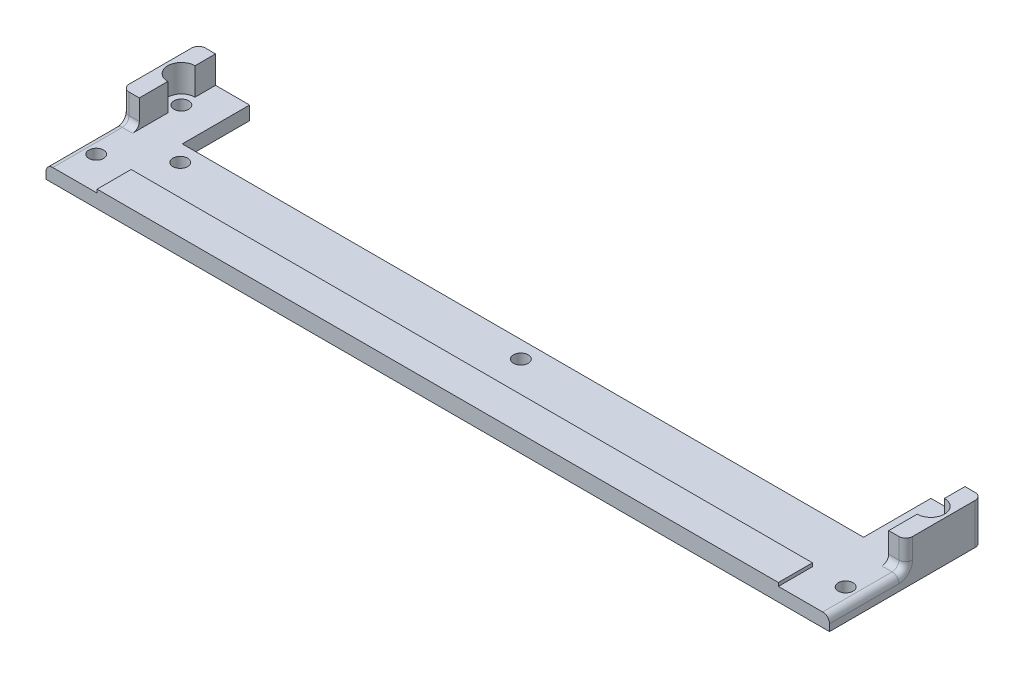
SolidWorks part; units mm, degrees
ref_plane "Front Plane" through (0, 0, 0) normal (0, 0, 1) x (1, 0, 0)
ref_plane "Top Plane" through (0, 0, 0) normal (0, 1, 0) x (1, 0, 0)
ref_plane "Right Plane" through (0, 0, 0) normal (1, 0, 0) x (0, 0, -1)
sketch "Sketch1" plane through (0, 0, 0) normal (0, 1, 0) x (1, 0, 0)
  line L0 (-139.7, 33.3321) -> (-139.7, 40.988)
  line L1 (-127, -15.875) -> (127, -15.875)
  line L2 (-127, -15.875) -> (-127, 15.875)
  line L3 (-127, 15.875) -> (127, 15.875)
  line L4 (127, -15.875) -> (127, 15.875)
  line L5 (-127, -15.875) -> (127, 15.875) construction
  line L6 (-127, 15.875) -> (127, -15.875) construction
  line L7 (-127, -15.875) -> (-146.05, -15.875)
  line L8 (-127, -15.875) -> (-127, 40.988)
  line L9 (-127, 40.988) -> (-146.05, 40.988)
  line L10 (-146.05, -15.875) -> (-146.05, 40.988)
  line L11 (127, -15.875) -> (146.05, -15.875)
  line L12 (127, -15.875) -> (127, 40.988)
  line L13 (127, 40.988) -> (146.05, 40.988)
  line L14 (146.05, -15.875) -> (146.05, 40.988)
  line L15 (-139.7, 23.1721) -> (-139.7, 1.5821)
  line L16 (-139.7, 33.3321) -> (-139.7, 31.0021)
  line L17 (-139.7, 25.5021) -> (-139.7, 23.1721)
  line L18 (-139.7, 1.5821) -> (-139.7, -0.7479)
  line L19 (-139.7, -6.2479) -> (-139.7, -15.875)
  line L20 (0, 15.875) -> (0, -15.875) construction
  line L21 (139.7, 1.5821) -> (139.7, -0.7479)
  line L22 (139.7, -6.2479) -> (139.7, -15.875)
  line L23 (139.7, 23.1721) -> (139.7, 1.5821)
  line L24 (139.7, 25.5021) -> (139.7, 23.1721)
  line L25 (139.7, 33.3321) -> (139.7, 31.0021)
  line L26 (139.7, 33.3321) -> (139.7, 40.988)
  line L27 (139.7, 40.988) -> (139.7, 31.0021)
  line L28 (139.7, 23.1721) -> (139.7, 25.5021)
  line L29 (139.7, 23.1721) -> (139.7, -0.7479)
  line L30 (139.7, -6.2479) -> (139.7, -15.875)
  circle A0 centre (-139.7, 28.2521) radius 2.75
  circle A1 centre (-139.7, -3.4979) radius 2.75
  circle A2 centre (139.7, 28.2521) radius 2.75
  circle A3 centre (139.7, -3.4979) radius 2.75
  arc A4 (-139.7, 33.3321) -> (-139.7, 23.1721) centre (-139.7, 28.2521) ccw
  arc A5 (-139.7, 1.5821) -> (-139.7, -8.5779) centre (-139.7, -3.4979) ccw
  arc A6 (139.7, -8.5779) -> (139.7, 1.5821) centre (139.7, -3.4979) ccw
  arc A7 (139.7, 23.1721) -> (139.7, 33.3321) centre (139.7, 28.2521) ccw
  circle A8 centre (5.588, 9.525) radius 2.75
  circle A9 centre (-121.412, 9.525) radius 2.75
  point P0 (0, 0)
  dimension "D5" = 5.5
  dimension "D6" = 10.16
  dimension "D7" = 10.16
  dimension "D8" = 254
  dimension "D9" = 31.75
  dimension "D11" = 5.5
  dimension "D13" = 5.5
  dimension "D1" = 31.75
  dimension "D2" = 279.4
  dimension "D3" = 292.1
  dimension "D4" = 6.35
  dimension "D10" = 121.412
  dimension "D12" = 5.588
  dimension "D14" = 6.35
  dimension "D15" = 6.35
extrude "Boss-Extrude1" add sketch "Sketch1" against normal blind 2.54 and the other way blind 2.54 contours A1 L19 L7 L2 L8 L9 L0 L16 A0 L17 L15 L18 | L1 L4 L3 L2 | A3 L21 L23 L24 A2 L25 L26 L13 L12 L4 L11 L30 L22 | A5 L15 A4 L0 L9 L10 L7 L19 | A7 L23 A6 L30 L11 L14 L13 L26 | L16 A4 L17 A0 | L18 A5 L19 A1 | L22 A6 L21 A3 | L24 A7 L25 A2 region at (-143.17, 0, -12.6084) region at (-133.1737, 0, -12.5626) region at (-139.8136, 0, -32.1671) region at (-139.8136, 0, -0.4171) region at (0.3432, 0, 0.0565) region at (133.1737, 0, -12.5626) region at (143.17, 0, -12.6084) region at (139.8136, 0, 7.4129) region at (144.6664, 0, -28.2521)
sketch "Sketch2" plane through (0, 2.54, 0) normal (0, 1, 0) x (1, 0, 0)
  line L0 (0, 15.875) -> (0, -15.875) construction
  line L1 (-127, 15.875) -> (127, 15.875) construction
  line L2 (146.05, -15.875) -> (-146.05, -15.875) construction
  line L3 (-139.7, 33.3321) -> (-139.7, 40.988)
  line L4 (-127, 40.988) -> (-146.05, 40.988) construction
  line L5 (-139.7, 23.1721) -> (-139.7, 12.5565)
  line L6 (-139.7, 12.5565) -> (-146.05, 12.5565)
  line L7 (-146.05, -15.875) -> (-146.05, 40.988) construction
  line L8 (-139.7, 40.988) -> (-146.05, 40.988)
  line L9 (-146.05, 40.988) -> (-146.05, 12.5565)
  line L10 (146.05, 40.988) -> (146.05, 12.5565)
  line L11 (139.7, 40.988) -> (146.05, 40.988)
  line L12 (139.7, 12.5565) -> (146.05, 12.5565)
  line L13 (139.7, 23.1721) -> (139.7, 12.5565)
  line L14 (139.7, 33.3321) -> (139.7, 40.988)
  arc A0 (-139.7, 33.3321) -> (-139.7, 23.1721) centre (-139.7, 28.2521) ccw
  arc A1 (139.7, 33.3321) -> (139.7, 23.1721) centre (139.7, 28.2521) cw
  dimension "D1" = 10.16
extrude "Boss-Extrude2" add sketch "Sketch2" along normal blind 10.16
fillet "Fillet1" radius 2.54 8 edges at (146.05, 7.62, -12.5565) (-146.05, 2.54, 1.6593) (146.05, 5.08, -40.988) (142.875, 2.54, -12.5565) (146.05, 2.54, 1.6593) (-146.05, 5.08, -40.988) (-146.05, 7.62, -12.5565) (-142.875, 2.54, -12.5565)
sketch "Sketch3" plane through (0, 2.54, 0) normal (0, 1, 0) x (1, 0, 0)
  line L0 (143.51, -15.875) -> (-143.51, -15.875) construction
  line L1 (-127, -15.875) -> (127, -15.875)
  line L2 (-127, -15.875) -> (-127, -3.175)
  line L3 (-127, -3.175) -> (127, -3.175)
  line L4 (127, -15.875) -> (127, -3.175)
  dimension "D1" = 12.7
extrude "Boss-Extrude3" add sketch "Sketch3" along normal blind 1.27
